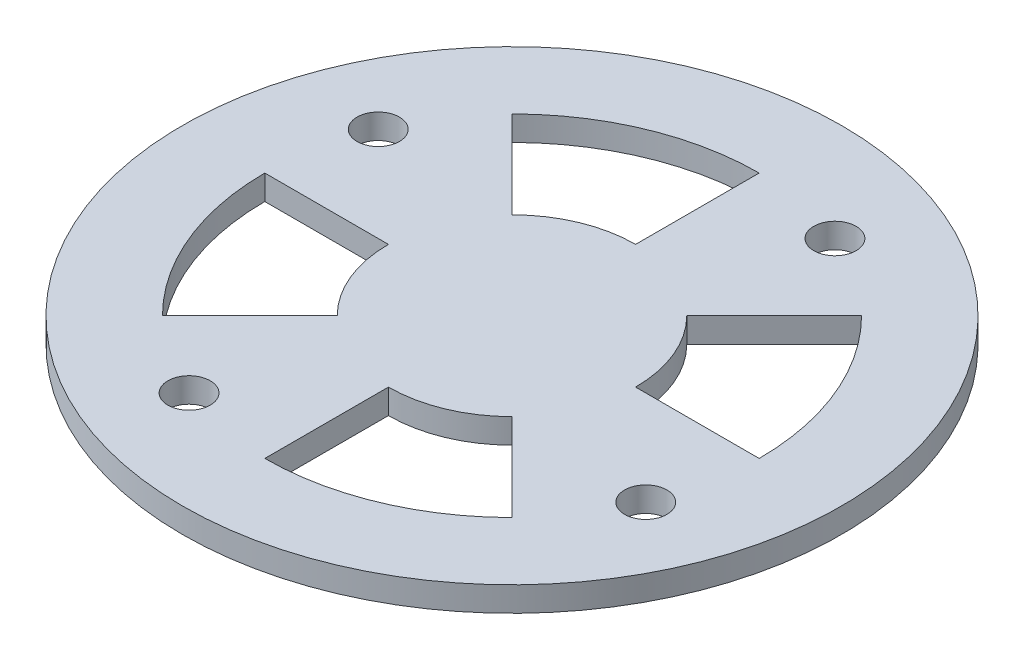
SolidWorks part; units mm, degrees
ref_plane "Front Plane" through (0, 0, 0) normal (0, 0, 1) x (1, 0, 0)
ref_plane "Top Plane" through (0, 0, 0) normal (0, 1, 0) x (1, 0, 0)
ref_plane "Right Plane" through (0, 0, 0) normal (1, 0, 0) x (0, 0, -1)
sketch "Sketch1" plane through (0, 0, 0) normal (0, 1, 0) x (1, 0, 0)
  circle A0 centre (0, 0) radius 50.8
  dimension "D1" = 101.6
extrude "Boss-Extrude1" add sketch "Sketch1" along normal blind 3.81
sketch "Sketch2" plane through (0, 3.81, 0) normal (0, 1, 0) x (1, 0, 0)
  line L0 (0, 0) -> (0, 38.1)
  line L1 (0, 0) -> (26.9408, 26.9408)
  line L2 (0, 0) -> (38.1, 0)
  line L3 (0, 0) -> (26.9408, -26.9408)
  line L4 (0, 0) -> (0, -38.1)
  line L5 (0, 0) -> (-26.9408, -26.9408)
  line L6 (0, 0) -> (-38.1, 0)
  line L7 (0, 0) -> (-26.9408, 26.9408)
  circle A0 centre (0, 0) radius 38.1
  circle A1 centre (0, 0) radius 19.05
  point P11 (-13.7464, 2.2911)
  point P12 (0, 0)
  dimension "D1" = 38.1
  dimension "D2" = 76.2
  dimension "D3" = 45
extrude "Cut-Extrude1" cut sketch "Sketch2" against normal through all contours A1 L0 A0 L7 | A1 L6 A0 L5 | A1 L4 A0 L3 | A1 L2 A0 L1 region at (-11.051, 3.81, -26.6794) region at (26.6794, 3.81, -11.051) region at (11.051, 3.81, 26.6794) region at (-26.6794, 3.81, 11.051)
sketch "Sketch3" plane through (0, 3.81, 0) normal (0, 1, 0) x (1, 0, 0)
  line L0 (0, 0) -> (0, 38.1) construction
  line L1 (0, 0) -> (26.9408, 26.9408) construction
  line L2 (14.5802, 35.1998) -> (0, 0) construction
  circle A0 centre (14.5802, 35.1998) radius 3.2639
  circle A1 centre (35.1998, -14.5802) radius 3.2639
  circle A2 centre (-14.5802, -35.1998) radius 3.2639
  circle A3 centre (-35.1998, 14.5802) radius 3.2639
  point P8 (0, 0)
  point P17 (0, 0)
  dimension "D1" = 6.5278
  dimension "D2" = 22.5
  dimension "D3" = 38.1
  dimension "D4" = 4
extrude "Cut-Extrude2" cut sketch "Sketch3" against normal through all contours A0 | A1 | A2 | A3 region at (14.5802, 3.81, -35.1998) region at (35.1998, 3.81, 14.5802) region at (-14.5802, 3.81, 35.1998)
